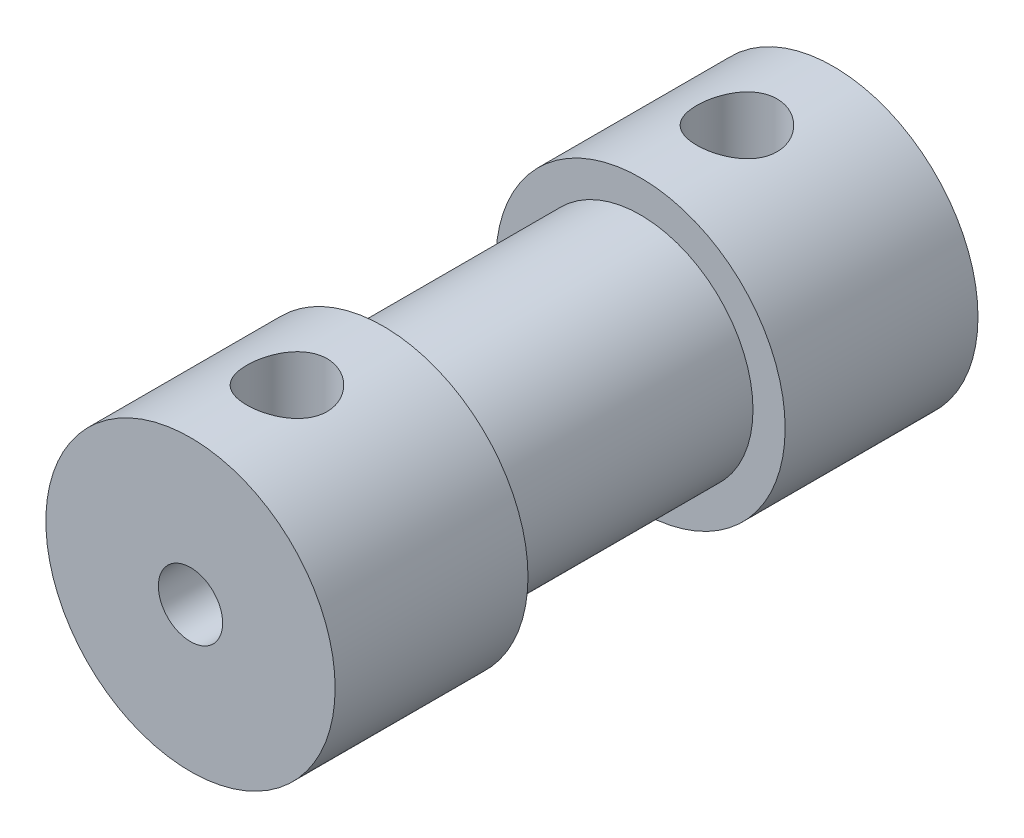
SolidWorks part; units mm, degrees
ref_plane "Front Plane" through (0, 0, 0) normal (0, 0, 1) x (1, 0, 0)
ref_plane "Top Plane" through (0, 0, 0) normal (0, 1, 0) x (1, 0, 0)
ref_plane "Right Plane" through (0, 0, 0) normal (1, 0, 0) x (0, 0, -1)
sketch "Sketch1" plane through (0, 0, 0) normal (0, 0, 1) x (1, 0, 0)
  circle A0 centre (0, 0) radius 4.5
  dimension "D1" = 9
extrude "Boss-Extrude1" add sketch "Sketch1" along normal blind 10 and the other way blind 10
sketch "Sketch2" plane through (0, 0, 0) normal (0, 0, 1) x (1, 0, 0)
  circle A0 centre (0, 0) radius 4.5
  circle A1 centre (0, 0) radius 4.5
  circle A2 centre (0, 0) radius 3.5
  dimension "D1" = 7
extrude "Cut-Extrude1" cut sketch "Sketch2" against normal blind 4 and the other way blind 4
sketch "Sketch3" plane through (0, 0, 10) normal (0, 0, 1) x (1, 0, 0)
  circle A0 centre (0, 0) radius 1
  dimension "D1" = 2
extrude "Cut-Extrude2" cut sketch "Sketch3" against normal blind 20
sketch "Sketch4" plane through (0, 0, -10) normal (0, 0, -1) x (-1, 0, 0)
  circle A0 centre (0, 0) radius 2
  dimension "D1" = 4
extrude "Cut-Extrude3" cut sketch "Sketch4" against normal blind 12
sketch "Sketch5" plane through (0, 0, 0) normal (0, 1, 0) x (1, 0, 0)
  line L0 (-4.5, 10) -> (-4.5, 4)
  line L1 (4.5, 4) -> (4.5, 10)
  line L2 (4.5, 4) -> (4.5, 10)
  line L3 (-4.5, 10) -> (-4.5, 4)
  line L4 (-4.5, -4) -> (-4.5, -10)
  line L5 (4.5, -10) -> (4.5, -4)
  line L6 (4.5, -10) -> (4.5, -4)
  line L7 (-4.5, -4) -> (-4.5, -10)
  line L8 (-4.5, 10) -> (4.5, 4) construction
  line L9 (4.5, 4) -> (4.5, 10) construction
  line L10 (4.5, 10) -> (-4.5, 4) construction
  line L11 (-4.5, -4) -> (4.5, -10) construction
  line L12 (4.5, -10) -> (4.5, -4) construction
  line L13 (4.5, -4) -> (-4.5, -10) construction
  circle A0 centre (0, 7) radius 1.25
  circle A1 centre (0, -7) radius 1.25
  dimension "D1" = 2.5
  dimension "D2" = 2.5
extrude "Cut-Extrude4" cut sketch "Sketch5" against normal blind 10 and the other way blind 10 contours A0 | A1
